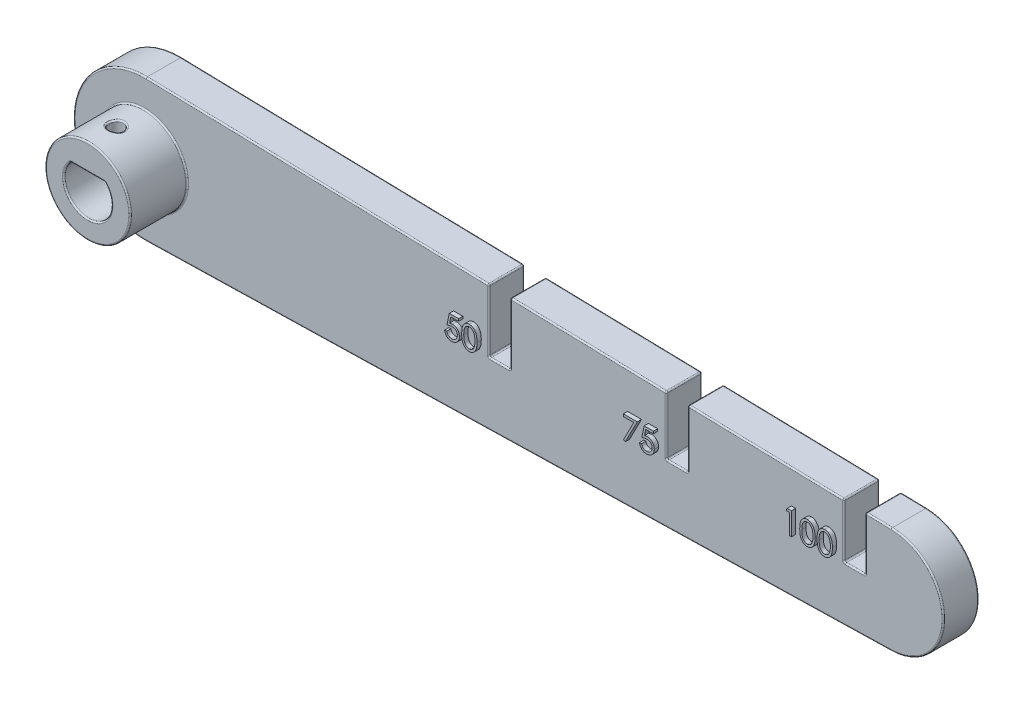
SolidWorks part; units mm, degrees
ref_plane "Front Plane" through (0, 0, 0) normal (0, 0, 1) x (1, 0, 0)
ref_plane "Top Plane" through (0, 0, 0) normal (0, 1, 0) x (1, 0, 0)
ref_plane "Right Plane" through (0, 0, 0) normal (1, 0, 0) x (0, 0, -1)
sketch "Sketch3" plane through (0, 0, 0) normal (0, 0, 1) x (1, 0, 0)
  line L0 (0.2381, 9.9972) -> (105.1786, 7.4979)
  line L1 (105.1786, -7.4979) -> (0.2381, -9.9972)
  arc A0 (0.2381, 9.9972) -> (0.2381, -9.9972) centre (0, 0) ccw
  arc A1 (105.1786, -7.4979) -> (105.1786, 7.4979) centre (105, 0) ccw
  dimension "D1" = 20
  dimension "D2" = 15
  dimension "D3" = 105
extrude "Boss-Extrude1" add sketch "Sketch3" along normal blind 5
sketch "Sketch2" plane through (0, 0, 0) normal (0, 0, 1) x (1, 0, 0)
  line L0 (-2.4, 2.3372) -> (2.4, 2.3372)
  arc A0 (2.4, 2.3372) -> (-2.4, 2.3372) centre (0, 0) cw
  dimension "D1" = 3.35
  dimension "D2" = 4.8
extrude "Cut-Extrude2" cut sketch "Sketch2" along normal up to next
sketch "Sketch4" plane through (0, 0, 5) normal (0, 0, 1) x (1, 0, 0)
  line L0 (105.1786, 7.4979) -> (0.2381, 9.9972) construction
  line L1 (98.5, 7.6569) -> (101.5, 7.6569)
  line L2 (98.5, 7.6569) -> (98.5, 0)
  line L3 (98.5, 0) -> (101.5, 0)
  line L4 (101.5, 7.6569) -> (101.5, 0)
  line L5 (100, 0) -> (100, 7.6212) construction
  line L6 (0, 0) -> (112.5, 0) construction
  line L7 (73.5, 8.2523) -> (76.5, 8.2523)
  line L8 (73.5, 8.2523) -> (73.5, 0)
  line L9 (73.5, 0) -> (76.5, 0)
  line L10 (76.5, 8.2523) -> (76.5, 0)
  line L11 (75, 0) -> (75, 8.2523) construction
  line L12 (48.5, 8.8477) -> (51.5, 8.8477)
  line L13 (48.5, 8.8477) -> (48.5, 0)
  line L14 (48.5, 0) -> (51.5, 0)
  line L15 (51.5, 8.8477) -> (51.5, 0)
  line L16 (50, 0) -> (50, 8.8477) construction
  arc A0 (105.1786, -7.4979) -> (105.1786, 7.4979) centre (105, 0) ccw construction
  dimension "D3" = 3
  dimension "D4" = 50
  dimension "D5" = 75
  dimension "D6" = 100
extrude "Cut-Extrude3" cut sketch "Sketch4" against normal up to next
sketch "Sketch6" plane through (0, 0, 5) normal (0, 0, 1) x (1, 0, 0)
  line L0 (-2.4, 2.3372) -> (2.4, 2.3372)
  circle A0 centre (0, 0) radius 6
  arc A1 (2.4, 2.3372) -> (-2.4, 2.3372) centre (0, 0) cw
  point P3 (-2.4, 2.3372)
  point P11 (0, 0)
  point P12 (-2.4, 2.3372)
  point P13 (-2.4, 2.3372)
  dimension "D1" = 12
extrude "Boss-Extrude3" add sketch "Sketch6" along normal blind 8
sketch "Sketch7" plane through (0, 0, 0) normal (0, 1, 0) x (1, 0, 0)
  line L0 (0, -5) -> (0, -13) construction
  line L1 (-6, -5) -> (6, -5) construction
  line L2 (-6, -13) -> (6, -13) construction
  circle A0 centre (0, -9) radius 1
  point P8 (0, 0)
  dimension "D1" = 2
extrude "Cut-Extrude4" cut sketch "Sketch7" along normal up to next
fillet "Fillet1" radius 0.2 54 edges at (51.5, 0, 2.5) (48.5, 0, 2.5) (101.5, 0, 2.5) (98.5, 0, 2.5) (76.5, 0, 2.5) (73.5, 0, 2.5) (0, 2.3372, 0) (0, -3.35, 0) (76.5, 4.0904, 0) (75, 0, 0) (73.5, 4.1262, 0) (62.5, 8.5143, 0) (51.5, 4.3881, 0) (50, 0, 0) (48.5, 4.4239, 0) (24.369, 9.4225, 0) (-10, 0, 0) (52.7083, -8.7475, 0) (112.5, 0, 0) (103.3393, 7.5417, 0) (101.5, 3.7927, 0) (100, 0, 0) (98.5, 3.8285, 0) (87.5, 7.9189, 0) (100, 0, 5) (101.5, 3.7927, 5) (103.3393, 7.5417, 5) (112.5, 0, 5) (52.7083, -8.7475, 5) (-10, 0, 5) (24.369, 9.4225, 5) (48.5, 4.4239, 5) (50, 0, 5) (51.5, 4.3881, 5) (62.5, 8.5143, 5) (73.5, 4.1262, 5) (75, 0, 5) (76.5, 4.0904, 5) (87.5, 7.9189, 5) (98.5, 3.8285, 5) (101.5, 7.5855, 2.5) (98.5, 7.6569, 2.5) (76.5, 8.1809, 2.5) (73.5, 8.2523, 2.5) (51.5, 8.7763, 2.5) (48.5, 8.8477, 2.5) (6, 0, 5) (0, 2.3372, 13) (2.4, 2.3372, 6.5) (0, -3.35, 13) (-2.4, 2.3372, 6.5) (-0.2145, 5.9962, 9.9767) (0, 2.3372, 8) (6, 0, 13)
sketch "Sketch5" plane through (0, 0, 5) normal (0, 0, 1) x (1, 0, 0)
  line L0 (0, 0) -> (112.3, 0) construction
  line L1 (48.5, 8.6525) -> (48.5, 0.2) construction
  line L2 (73.5, 8.057) -> (73.5, 0.2) construction
  line L3 (98.5, 7.4616) -> (98.5, 0.2) construction
  arc A0 (105.1738, -7.2979) -> (105.1738, 7.2979) centre (105, 0) ccw construction
  text T0 "50"
  text T1 "75"
  text T2 "100"
  dimension "D1" = 5.8
  dimension "D2" = 5.8
  dimension "D3" = 8.2
extrude "Boss-Extrude2" add sketch "Sketch5" along normal blind 0.6
